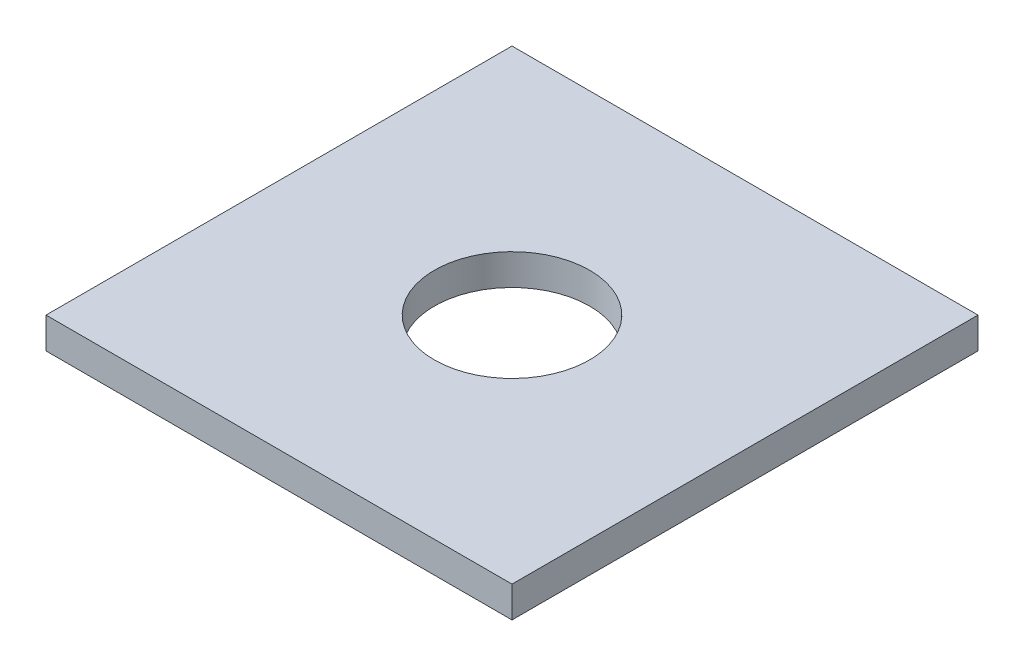
SolidWorks part; units mm, degrees
ref_plane "Plane1" through (0, 0, 0) normal (0, 0, 1) x (1, 0, 0)
ref_plane "Plane2" through (0, 0, 0) normal (0, 1, 0) x (1, 0, 0)
ref_plane "Plane3" through (0, 0, 0) normal (1, 0, 0) x (0, 0, -1)
sketch "Sketch1" plane through (0, 0, 0) normal (0, 0, 1) x (1, 0, 0)
  line L0 (-45, 0) -> (-45, 6)
  line L1 (-45, 6) -> (45, 6)
  line L2 (45, 6) -> (45, 0)
  line L3 (45, 0) -> (-45, 0)
extrude "Base-Extrude" add sketch "Sketch1" along normal mid plane 90
sketch "Sketch2" plane through (0, 6, 0) normal (0, 1, 0) x (-1, 0, 0)
  circle A0 centre (0, 0) radius 15
  dimension "HoleDia" = 30
extrude "Cut-Extrude1" cut sketch "Sketch2" against normal through all
equation "\"D1@Base-Extrude\" = \"SquareSize@Sketch1\""
